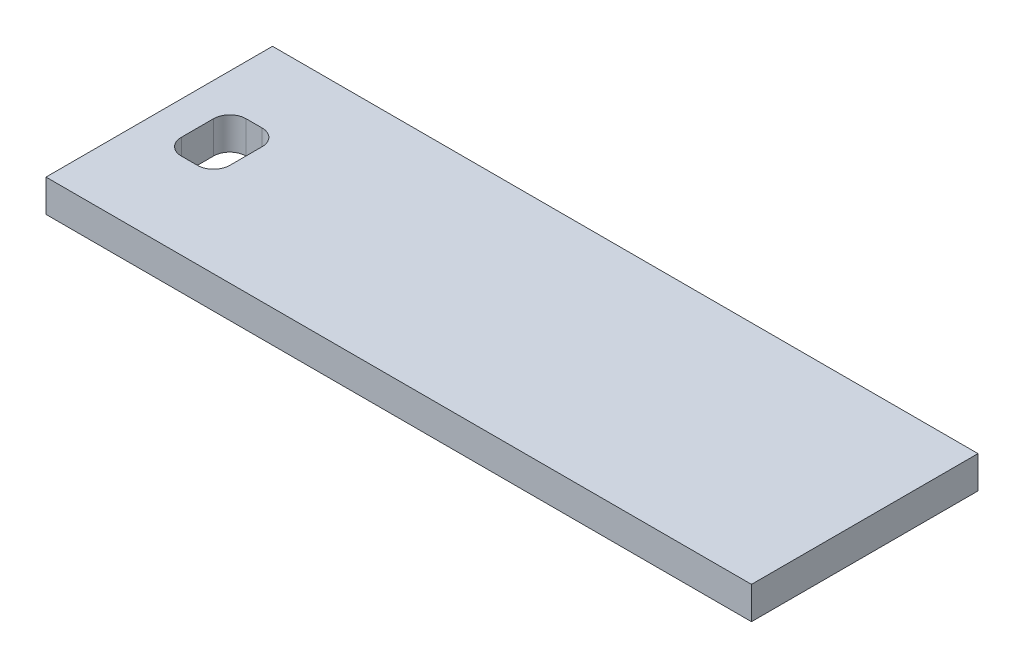
SolidWorks part; units mm, degrees
ref_plane "前视基准面" through (0, 0, 0) normal (0, 0, 1) x (1, 0, 0)
ref_plane "上视基准面" through (0, 0, 0) normal (0, 1, 0) x (1, 0, 0)
ref_plane "右视基准面" through (0, 0, 0) normal (1, 0, 0) x (0, 0, -1)
sketch "草图1" plane through (0, 0, 0) normal (0, 1, 0) x (1, 0, 0)
  line L1 (-109, 35) -> (109, 35)
  line L2 (-109, 35) -> (-109, -35)
  line L3 (-109, -35) -> (109, -35)
  line L4 (109, 35) -> (109, -35)
  line L5 (-109, 35) -> (109, -35) construction
  line L6 (-109, -35) -> (109, 35) construction
  point P0 (0, 0)
  dimension "D1" = 218
  dimension "D2" = 70
extrude "凸台-拉伸1" add sketch "草图1" along normal blind 10
sketch "草图2" plane through (0, 10, 0) normal (0, 1, 0) x (1, 0, 0)
  line L1 (-83.7348, -8.4712) -> (-98.7348, -8.4712)
  line L2 (-83.7348, -8.4712) -> (-83.7348, 11.5288)
  line L3 (-83.7348, 11.5288) -> (-98.7348, 11.5288)
  line L4 (-98.7348, -8.4712) -> (-98.7348, 11.5288)
  line L5 (-83.7348, -8.4712) -> (-98.7348, 11.5288) construction
  line L6 (-83.7348, 11.5288) -> (-98.7348, -8.4712) construction
  point P0 (-91.2348, 1.5288)
  dimension "D1" = 15
  dimension "D2" = 20
extrude "切除-拉伸1" cut sketch "草图2" against normal through all
fillet "圆角1" radius 5 4 edges at (-98.7348, 5, 8.4712) (-83.7348, 5, 8.4712) (-83.7348, 5, -11.5288) (-98.7348, 5, -11.5288)
